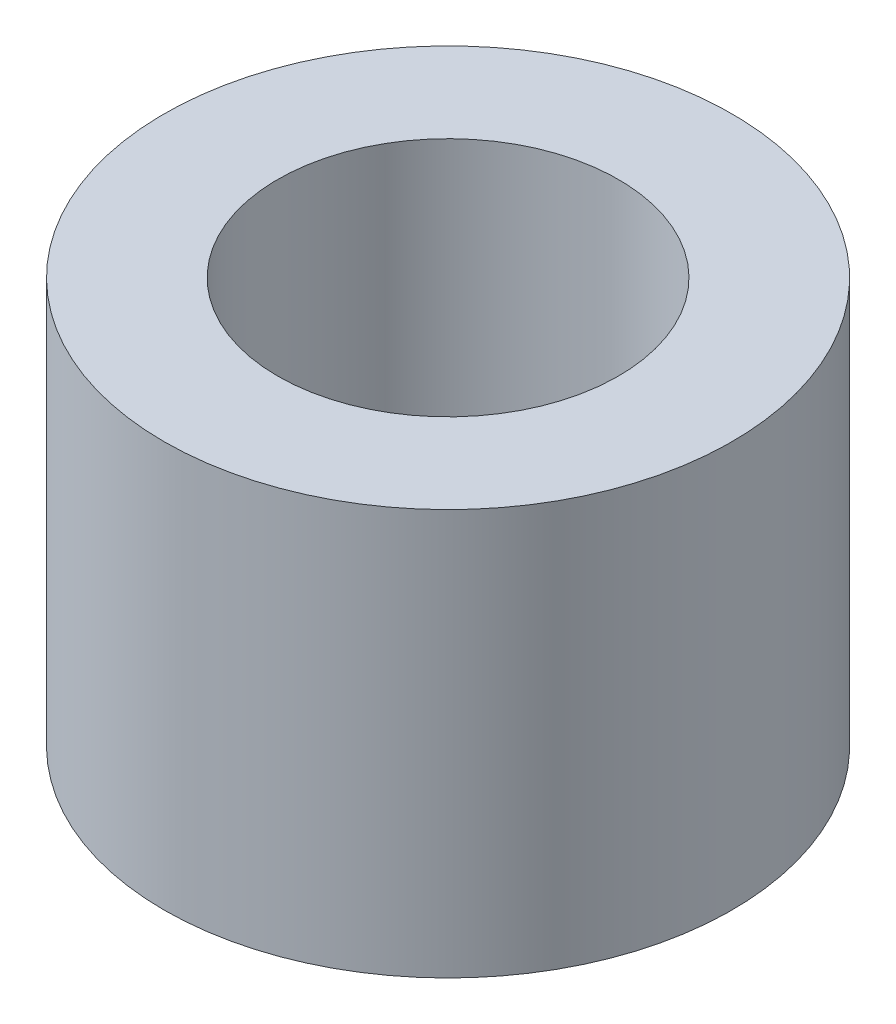
SolidWorks part; units mm, degrees
ref_plane "前视" through (0, 0, 0) normal (0, 0, 1) x (1, 0, 0)
ref_plane "上视" through (0, 0, 0) normal (0, 1, 0) x (1, 0, 0)
ref_plane "右视" through (0, 0, 0) normal (1, 0, 0) x (0, 0, -1)
sketch "草图1" plane through (0, 0, 0) normal (0, 1, 0) x (1, 0, 0)
  circle A0 centre (0, 0) radius 3.5
  circle A1 centre (0, 0) radius 2.1
  dimension "D1" = 4.2
  dimension "D2" = 7
extrude "凸台-拉伸1" add sketch "草图1" along normal blind 5
